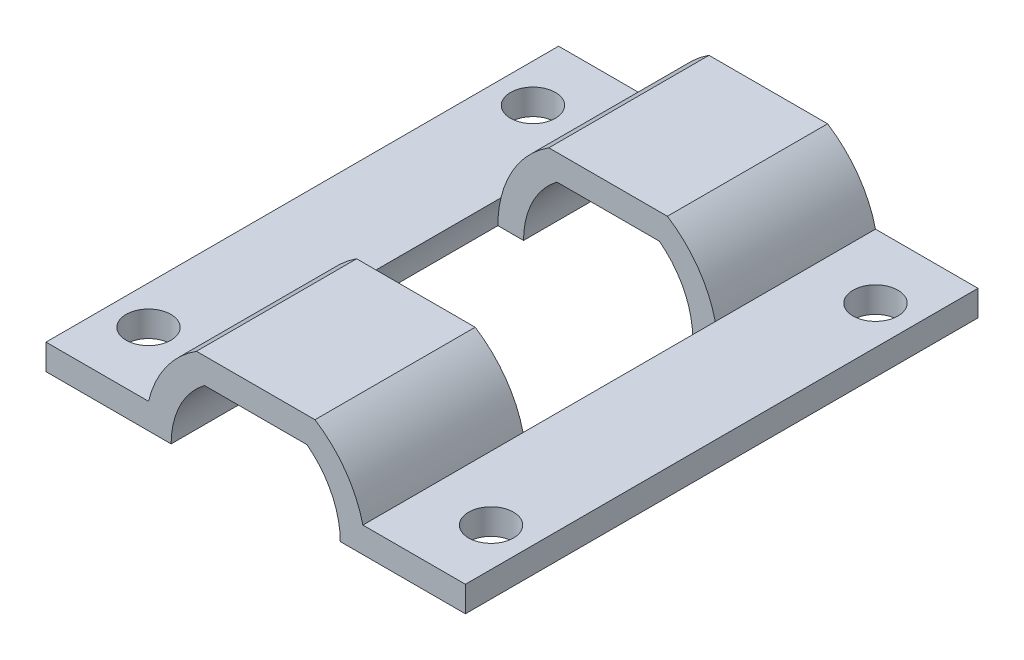
SolidWorks part; units mm, degrees
ref_plane "Front Plane" through (0, 0, 0) normal (0, 0, 1) x (1, 0, 0)
ref_plane "Top Plane" through (0, 0, 0) normal (0, 1, 0) x (1, 0, 0)
ref_plane "Right Plane" through (0, 0, 0) normal (1, 0, 0) x (0, 0, -1)
sketch "Sketch2" plane through (0, 0, 0) normal (0, 0, 1) x (1, 0, 0)
  line L0 (6.3377, 0) -> (-6.3377, 0) construction
  line L4 (-6.6, 0) -> (6.6, 0)
  line L6 (-3.9997, 5.25) -> (3.9997, 5.25)
  line L8 (-4.6257, 7.25) -> (4.6257, 7.25)
  line L9 (-8.3642, -2) -> (8.3642, -2) construction
  line L10 (0, 0) -> (0, 13.1029) construction
  line L11 (8.6, 0) -> (16.3642, 0)
  line L13 (8.3642, 2) -> (16.3642, 2)
  line L14 (16.3642, 0) -> (16.3642, 2)
  line L15 (-8.3642, 2) -> (-16.3642, 2)
  line L16 (-16.3642, 0) -> (-16.3642, 2)
  line L17 (-8.6, 0) -> (-16.3642, 0)
  line L19 (8.6, 0) -> (6.6, 0)
  line L20 (-6.6, 0) -> (-8.6, 0)
  arc A2 (6.6, 0) -> (3.9997, 5.25) centre (0, 0) ccw
  arc A3 (-3.9997, 5.25) -> (-6.6, 0) centre (0, 0) ccw
  arc A4 (-4.6257, 7.25) -> (-8.6, 0) centre (0, 0) ccw
  arc A5 (8.6, 0) -> (4.6257, 7.25) centre (0, 0) ccw
  arc A6 (8.3642, -2) -> (4.6257, 7.25) centre (0, 0) ccw construction
  arc A7 (-4.6257, 7.25) -> (-8.3642, -2) centre (0, 0) ccw construction
  point P6 (0, 0)
  point P27 (0, 0)
  point P28 (0, 0)
  dimension "D1" = 5.25
  dimension "D2" = 6.6
  dimension "D4" = 2
  dimension "D5" = 8
  dimension "D3" = 2
extrude "Boss-Extrude1" add sketch "Sketch2" along normal mid plane 40 contours A5 L11 L14 L13 | A4 L15 L16 L17 region at (-12.4427, 1.005, 0) region at (12.4427, 1.005, 0)
extrude "Boss-Extrude2" add sketch "Sketch2<4>" along normal mid plane 40 contours L19 A5 L8 A4 L20 A3 L6 A2 region at (-7.6, 0.1867, 0)
sketch "Sketch2<4>" plane through (0, 0, 0) normal (0, 0, 1) x (1, 0, 0) same geometry as "Sketch2"
extrude "Cut-Extrude1" cut sketch "Sketch2<5>" against normal mid plane 15 contours L19 A5 L8 A4 L20 A3 L6 A2 region at (-7.6, 0.1867, 0)
sketch "Sketch2<5>" plane through (0, 0, 0) normal (0, 0, 1) x (1, 0, 0) same geometry as "Sketch2"
sketch "Sketch3" plane through (0, 2, 0) normal (0, 1, 0) x (1, 0, 0)
  line L0 (-13.3642, 16.1704) -> (-13.3642, -15.5826) construction
  line L1 (-16.3642, -20) -> (-16.3642, 20) construction
  line L2 (-8.3642, 20) -> (-16.3642, 20) construction
  line L3 (-8.3642, -20) -> (-16.3642, -20) construction
  circle A0 centre (-13.3642, 15) radius 1.75
  circle A1 centre (-13.3642, -15) radius 1.75
  dimension "D1" = 3.5
  dimension "D2" = 3
  dimension "D3" = 5
  dimension "D4" = 5
extrude "Cut-Extrude2" cut sketch "Sketch3" against normal through all
mirror "Mirror1" about plane through (0, 0, 0) normal (1, 0, 0) of "Cut-Extrude2"
